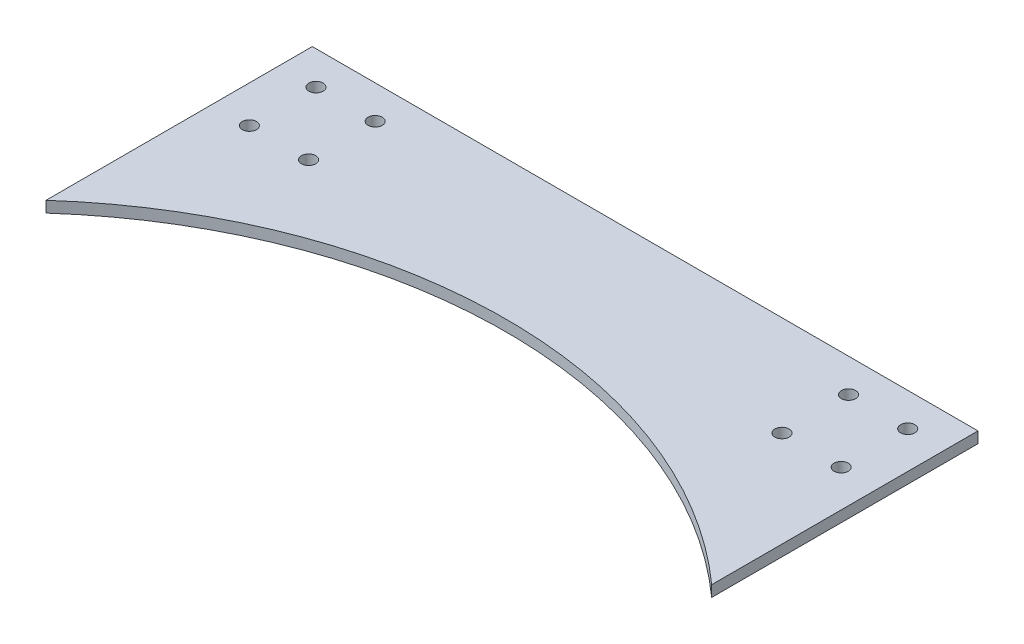
SolidWorks part; units mm, degrees
ref_plane "Front Plane" through (0, 0, 0) normal (0, 0, 1) x (1, 0, 0)
ref_plane "Top Plane" through (0, 0, 0) normal (0, 1, 0) x (1, 0, 0)
ref_plane "Right Plane" through (0, 0, 0) normal (1, 0, 0) x (0, 0, -1)
sketch "Sketch1" plane through (0, 0, 0) normal (0, 1, 0) x (1, 0, 0)
  line L0 (0, 0) -> (0, 76.2)
  line L1 (0, 76.2) -> (190.5, 76.2)
  line L2 (190.5, 76.2) -> (190.5, 0)
  arc A0 (0, 0) -> (190.5, 0) centre (95.25, -106.4927) cw
  point P6 (65.1348, 0)
  point P7 (0, 0)
  point P8 (63.5, -12.647)
  point P9 (63.5, -12.647)
  dimension "D3" = 142.875
  dimension "D1" = 76.2
  dimension "D2" = 190.5
extrude "Boss-Extrude1" add sketch "Sketch1" along normal blind 3.175
sketch "Sketch3" plane through (0, 0, 0) normal (0, -1, 0) x (1, 0, 0)
  circle A0 centre (10.5833, -66.675) radius 2.032 construction
  circle A1 centre (10.5833, -47.625) radius 2.032 construction
  circle A2 centre (27.5167, -47.625) radius 2.032 construction
  circle A3 centre (27.5167, -66.675) radius 2.032 construction
  circle A4 centre (162.9833, -66.675) radius 2.032 construction
  circle A5 centre (162.9833, -47.625) radius 2.032 construction
  circle A6 centre (179.9167, -47.625) radius 2.032 construction
  circle A7 centre (179.9167, -66.675) radius 2.032 construction
  circle A8 centre (10.5833, -66.675) radius 2.032
  circle A9 centre (10.5833, -47.625) radius 2.032
  circle A10 centre (27.5167, -47.625) radius 2.032
  circle A11 centre (27.5167, -66.675) radius 2.032
  circle A12 centre (162.9833, -66.675) radius 2.032
  circle A13 centre (162.9833, -47.625) radius 2.032
  circle A14 centre (179.9167, -47.625) radius 2.032
  circle A15 centre (179.9167, -66.675) radius 2.032
extrude "Cut-Extrude1" cut sketch "Sketch3" against normal through all
